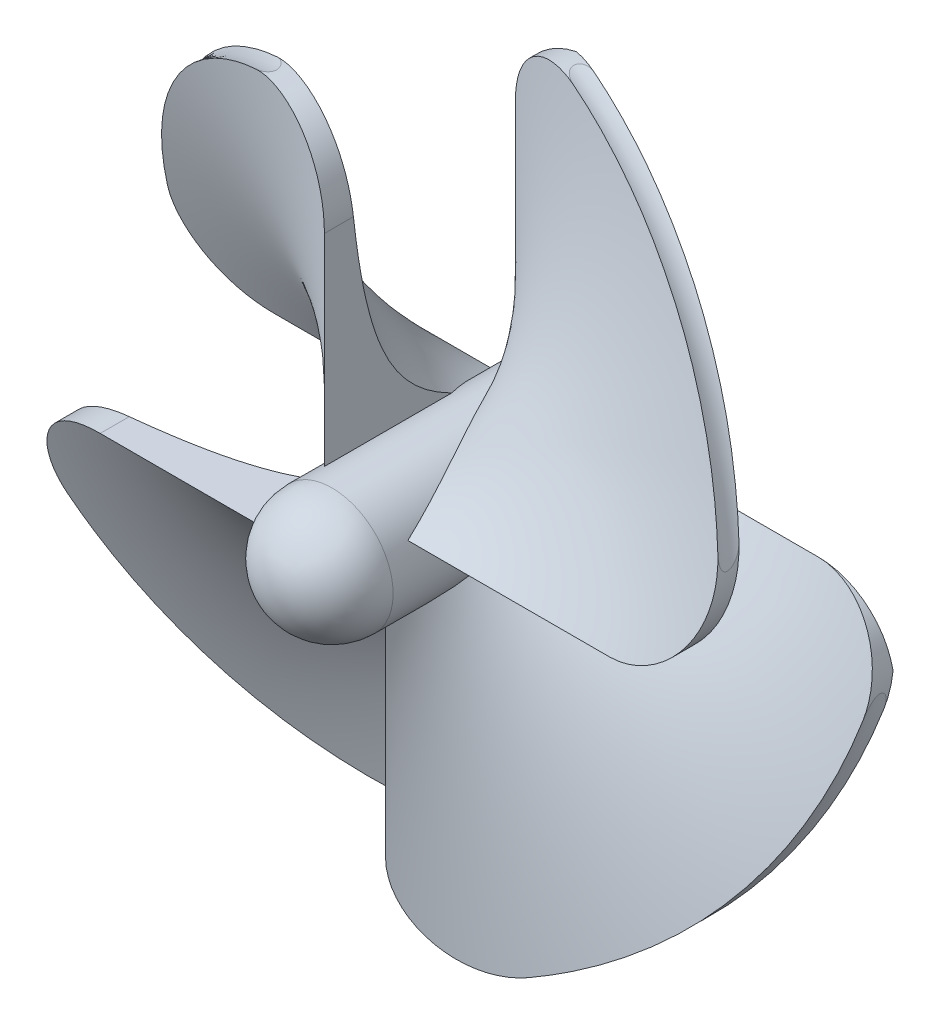
SolidWorks part; units mm, degrees
ref_plane "Front Plane" through (0, 0, 0) normal (0, 0, 1) x (1, 0, 0)
ref_plane "Top Plane" through (0, 0, 0) normal (0, 1, 0) x (1, 0, 0)
ref_plane "Right Plane" through (0, 0, 0) normal (1, 0, 0) x (0, 0, -1)
sketch "Sketch1" plane through (0, 0, 0) normal (0, 0, 1) x (1, 0, 0)
  circle A2 centre (0, 0) radius 1.905
  dimension "D1" = 3.81
curve "Helix/Spiral1" pitch 31.75 height 7.9375 radius 1.905 left hand yes centre (0, 0, 0) axis (0, 0, 1) start towards (-1, 0, 0)
sketch "Sketch4" plane through (0, 0, 0) normal (0, 0, 1) x (1, 0, 0)
  line L0 (0, 0) -> (-14.605, 0) construction
  line L1 (-14.605, -1.27) -> (-1.905, -1.27)
  line L2 (-14.605, -1.27) -> (-14.605, 1.27)
  line L3 (-14.605, 1.27) -> (-1.905, 1.27)
  line L4 (-1.905, -1.27) -> (-1.905, 1.27)
  line L5 (-14.605, -1.27) -> (-1.905, 1.27) construction
  line L6 (-14.605, 1.27) -> (-1.905, -1.27) construction
  spline S0 degree 3 poles (-1.905, 0) (-1.905, 0.2492) (-1.8058, 0.7481) (-1.3821, 1.3821) (-0.7481, 1.8058) (-0.2492, 1.905) (0, 1.905) knots 0 0 0 0 0.25 0.5 0.75 1 1 1 1 construction
  point P0 (-8.255, 0)
  point P8 (-5.3718, 0)
  dimension "D1" = 1.27
  dimension "length of blade" = 12.7
sweep "Sweep1" add profiles "Sketch4" path "Helix/Spiral1"
sketch "Sketch6" plane through (0, 0, 0) normal (0, 0, 1) x (1, 0, 0)
  line L0 (-14.605, -1.27) -> (-1.905, -1.27) construction
  line L1 (-1.27, 1.905) -> (-1.27, 14.605) construction
  line L2 (-11.326, -1.27) -> (-1.905, -1.27)
  line L3 (-1.27, 1.905) -> (-1.27, 10.5901)
  line L4 (0, 0) -> (0, -3.8822) construction
  line L5 (3.81, -21.5139) -> (-21.59, -21.5139)
  line L6 (3.81, -21.5139) -> (3.81, 16.5861)
  line L7 (3.81, 16.5861) -> (-21.59, 16.5861)
  line L8 (-21.59, -21.5139) -> (-21.59, 16.5861)
  line L9 (0, 0) -> (3.81, 0) construction
  arc A0 (-14.457, 2.4316) -> (-11.326, -1.27) centre (-11.326, 1.905) ccw
  arc A1 (-5.6738, 13.5177) -> (-1.27, 10.5901) centre (-4.445, 10.5901) cw
  spline S0 degree 2 poles (14.3193, -3.1427) (-139.0201, -701.8222) (-14.436, 2.5533) (-14.0999, 4.4539) (-13.2833, 6.2026) (-12.4667, 7.9514) (-11.2253, 9.4293) (-9.9839, 10.9071) (-8.4024, 12.0133) (-6.8208, 13.1195) (-5.0068, 13.7786) (667.2627, 258.0627) (5.5671, -13.5619) knots -3.668551 -3.668551 -3.668551 0.041667 0.041667 0.083333 0.083333 0.125 0.125 0.166667 0.166667 0.208333 0.208333 3.918512 3.918512 3.918512 weights 135.14468 0.238206 1 0.991445 1 0.991445 1 0.991445 1 0.991445 1 0.238214 135.141851 only from (-14.605, -1.27) to (-1.27, 14.605) construction
  spline S1 degree 2 poles (-14.457, 2.4316) (-14.4468, 2.4925) (-14.436, 2.5533) (-14.0999, 4.4539) (-13.2833, 6.2026) (-12.4667, 7.9514) (-11.2253, 9.4293) (-9.9839, 10.9071) (-8.4024, 12.0133) (-7.1185, 12.9113) (-5.6738, 13.5177) knots 0.040322 0.040322 0.040322 0.041667 0.041667 0.083333 0.083333 0.125 0.125 0.166667 0.166667 0.200545 0.200545 0.200545 weights 0.999466 0.999724 1 0.991445 1 0.991445 1 0.991445 1 0.993044 0.9974
  spline S2 degree 2 poles (-1.905, -1.27) (-2.0722, -1.0192) (-2.1688, -0.7337) (-2.2654, -0.4481) (-2.2848, -0.1474) (-2.3042, 0.1534) (-2.2451, 0.449) (-2.186, 0.7446) (-2.0524, 1.0148) (-1.9188, 1.285) (-1.7198, 1.5114) (-1.5208, 1.7378) (-1.27, 1.905) knots 0 0 0 0.041667 0.041667 0.083333 0.083333 0.125 0.125 0.166667 0.166667 0.208333 0.208333 0.25 0.25 0.25 weights 1 0.991445 1 0.991445 1 0.991445 1 0.991445 1 0.991445 1 0.991445 1 construction
  spline S3 degree 2 poles (-1.905, -1.27) (-2.0722, -1.0192) (-2.1688, -0.7337) (-2.2654, -0.4481) (-2.2848, -0.1474) (-2.3042, 0.1534) (-2.2451, 0.449) (-2.186, 0.7446) (-2.0524, 1.0148) (-1.9188, 1.285) (-1.7198, 1.5114) (-1.5208, 1.7378) (-1.27, 1.905) knots 0 0 0 0.041667 0.041667 0.083333 0.083333 0.125 0.125 0.166667 0.166667 0.208333 0.208333 0.25 0.25 0.25 weights 1 0.991445 1 0.991445 1 0.991445 1 0.991445 1 0.991445 1 0.991445 1
  point P19 (0, 0)
  dimension "D1" = 3.175
  dimension "D2" = 3.175
  dimension "D3" = 38.1
  dimension "D4" = 25.4
  dimension "D5" = 3.81
extrude "Cut-Extrude3" cut sketch "Sketch6" along normal through all contours A0 S1 A1 L5 region at (-9.2366, -3.9927, 0)
extrude "Boss-Extrude1" add sketch "Sketch1<2>" along normal blind 3.175 separate body contours A2
sketch "Sketch1<2>" plane through (0, 0, 0) normal (0, 0, 1) x (1, 0, 0) same geometry as "Sketch1"
sketch "Sketch7" plane through (0, 0, 0) normal (0, 0, 1) x (1, 0, 0)
  circle A0 centre (0, 0) radius 2.54
  point P4 (0, 0)
  dimension "D1" = 5.08
extrude "Boss-Extrude2" add sketch "Sketch7" along normal blind 8.89
ref_axis "Axis1" through (0, 0, 0) along (0, 0, 1)
pattern_circular "CirPattern1" count 4 every 90 about axis through (0, 0, 0) along (0, 0, 1) of bodies 106
sketch "Sketch10" plane through (0, 0, 8.89) normal (0, 0, 1) x (1, 0, 0)
  line L0 (0, 2.54) -> (0, -2.54) construction
  line L1 (0, 2.54) -> (0, -2.54)
  circle A0 centre (0, 0) radius 2.54 construction
  arc A1 (0, -2.54) -> (0, 2.54) centre (0, 0) ccw
revolve "Revolve1" add sketch "Sketch10" angle 360 about L0
sketch "Sketch11" plane through (0, 0, 0) normal (0, 0, -1) x (-1, 0, 0)
  line L0 (-0.375, 1.5226) -> (-0.375, 0.2726)
  line L1 (-0.375, 1.5226) -> (0.375, 1.5226)
  line L2 (-0.375, 0.2726) -> (0.375, 0.2726)
  line L3 (0.375, 1.5226) -> (0.375, 0.2726)
  line L4 (0, 0) -> (0, 1.5226) construction
  line L5 (0, 0.2726) -> (0, 1.5226) construction
  circle A0 centre (0, 0) radius 1
  dimension "D1" = 2
  dimension "D2" = 0.75
  dimension "D3" = 1.25
extrude "Cut-Extrude5" cut sketch "Sketch11" against normal blind 3.81 contours L0 A0 L3 L2 | A0 L3 L1 L0 | L3 A0 L0 L2 region at (0, 1.2489, 0) region at (0, 0.6247, 0) region at (0, -0.1261, 0)
